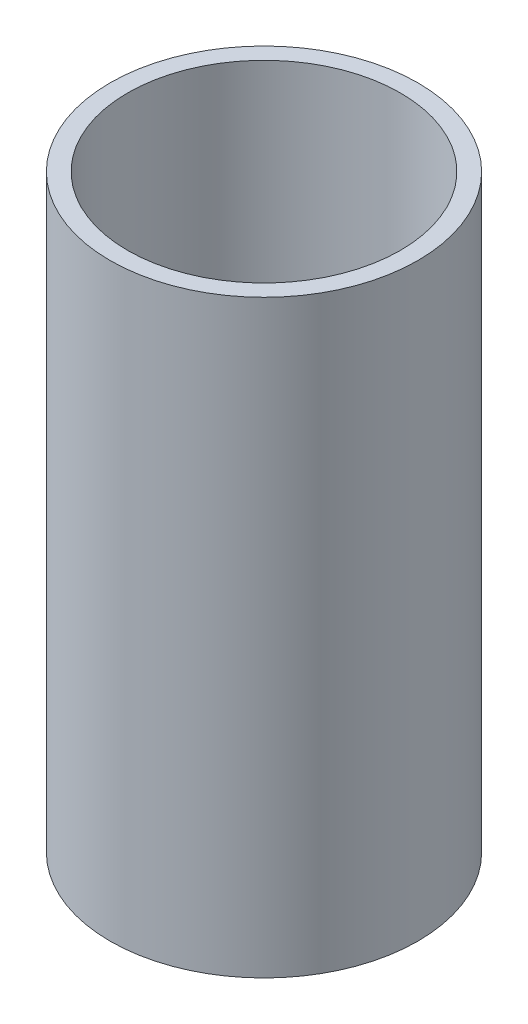
SolidWorks part; units mm, degrees
ref_plane "Front Plane" through (0, 0, 0) normal (0, 0, 1) x (1, 0, 0)
ref_plane "Top Plane" through (0, 0, 0) normal (0, 1, 0) x (1, 0, 0)
ref_plane "Right Plane" through (0, 0, 0) normal (1, 0, 0) x (0, 0, -1)
sketch "Sketch1" plane through (0, 0, 0) normal (0, 1, 0) x (1, 0, 0)
  circle A0 centre (0, 0) radius 37.5
  dimension "SLEEVE_OD" = 75
extrude "Boss-Extrude1" add sketch "Sketch1" along normal blind 143.6401
sketch "Sketch2" plane through (0, 0, 0) normal (0, 1, 0) x (1, 0, 0)
  circle A0 centre (0, 0) radius 33.2371
  dimension "BORE_D" = 66.4741
extrude "Cut-Extrude1" cut sketch "Sketch2" along normal through all
chamfer "Chamfer1" distance 2.8273 angle 45 rebuild error yes
